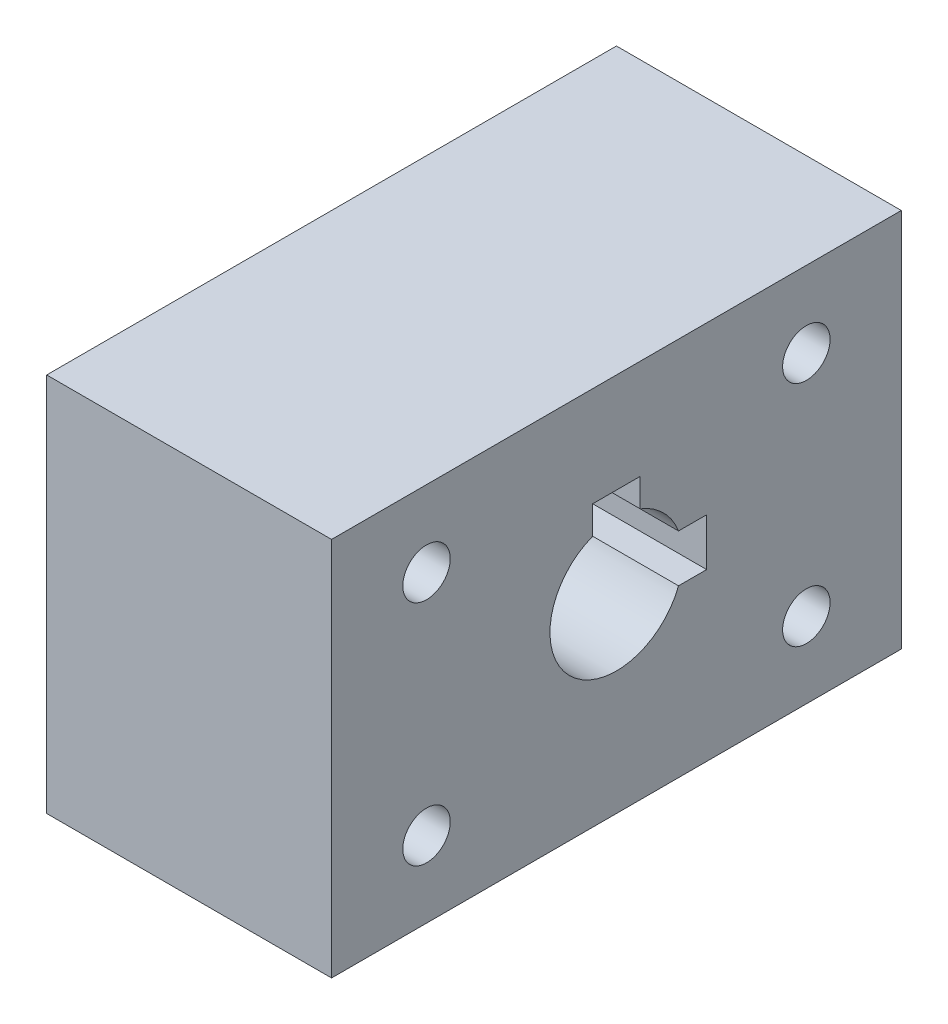
SolidWorks part; units mm, degrees
material "Plain Carbon Steel"
ref_plane "Front Plane" through (0, 0, 0) normal (0, 0, 1) x (1, 0, 0)
ref_plane "Top Plane" through (0, 0, 0) normal (0, 1, 0) x (1, 0, 0)
ref_plane "Right Plane" through (0, 0, 0) normal (1, 0, 0) x (0, 0, -1)
sketch "Sketch1" plane through (0, 0, 0) normal (1, 0, 0) x (0, 0, -1)
  line L1 (30, -20) -> (-30, -20)
  line L2 (30, -20) -> (30, 20)
  line L3 (30, 20) -> (-30, 20)
  line L4 (-30, -20) -> (-30, 20)
  line L5 (30, -20) -> (-30, 20) construction
  line L6 (30, 20) -> (-30, -20) construction
  point P0 (0, 0)
  dimension "D1" = 60
  dimension "D2" = 40
extrude "Boss-Extrude1" add sketch "Sketch1" along normal blind 30
sketch "Sketch2" plane through (30, 0, 0) normal (1, 0, 0) x (0, 0, -1)
  line L1 (2.5, 4.5) -> (-2.5, 4.5)
  line L2 (2.5, 4.5) -> (2.5, 9.5)
  line L3 (2.5, 9.5) -> (-2.5, 9.5)
  line L4 (-2.5, 4.5) -> (-2.5, 9.5)
  line L5 (2.5, 4.5) -> (-2.5, 9.5) construction
  line L6 (2.5, 9.5) -> (-2.5, 4.5) construction
  line L7 (4.5, -2.5) -> (9.5, -2.5)
  line L8 (4.5, -2.5) -> (4.5, 2.5)
  line L9 (4.5, 2.5) -> (9.5, 2.5)
  line L10 (9.5, -2.5) -> (9.5, 2.5)
  line L11 (4.5, -2.5) -> (9.5, 2.5) construction
  line L12 (4.5, 2.5) -> (9.5, -2.5) construction
  circle A0 centre (0, 0) radius 7
  point P3 (0, 7)
  point P8 (7, 0)
  dimension "D1" = 14
  dimension "D2" = 5
extrude "Cut-Extrude1" cut sketch "Sketch2" against normal through all contours L9 A0 L2 L1 L4 L7 L8 | L2 A0 L4 L1 | A0 L2 L3 L4 | L7 A0 L9 L8 | A0 L7 L10 L9 region at (30, -0.511, 0.511) region at (30, 5.6781, 0) region at (30, 8.1706, 0) region at (30, 0, -5.6781) region at (30, 0, -8.1706)
hole_wizard "Ø5.0 (5) Diameter Hole1" positions "Sketch5" profile "Sketch4" hole size "Ø5.0" standard "ISO" end condition through all
sketch "Sketch5" plane through (0, 0, 0) normal (-1, 0, 0) x (0, 0, 1)
  line L0 (-20, 20) -> (-20, 12) construction
  line L1 (-30, 20) -> (30, 20) construction
  line L2 (-20, 12) -> (-20, -12) construction
  line L3 (-20, -12) -> (-20, -20) construction
  line L4 (30, -20) -> (-30, -20) construction
  line L6 (-30, -20) -> (-30, 20) construction
  point P0 (-20, 12)
  point P2 (-20, -12)
  point P16 (-29.5615, 11.7987)
  dimension "D1" = 8
  dimension "D2" = 10
sketch "Sketch4" plane through (0, 12, -20) normal (0, 1, 0) x (0, 0, 1)
  line L0 (0, 0) -> (0, 30)
  line L1 (0, 30) -> (2.5, 30)
  line L2 (2.5, 30) -> (2.5, 0)
  line L5 (2.5, 0) -> (0, 0)
  line L11 (0, -6.35) -> (0, 107.95) construction
  dimension "Thru Hole Dia." = 5
  dimension "Thru Hole Depth" = 30
mirror "Mirror1" about plane through (0, 0, 0) normal (0, 0, 1) of "Ø5.0 (5) Diameter Hole1"
